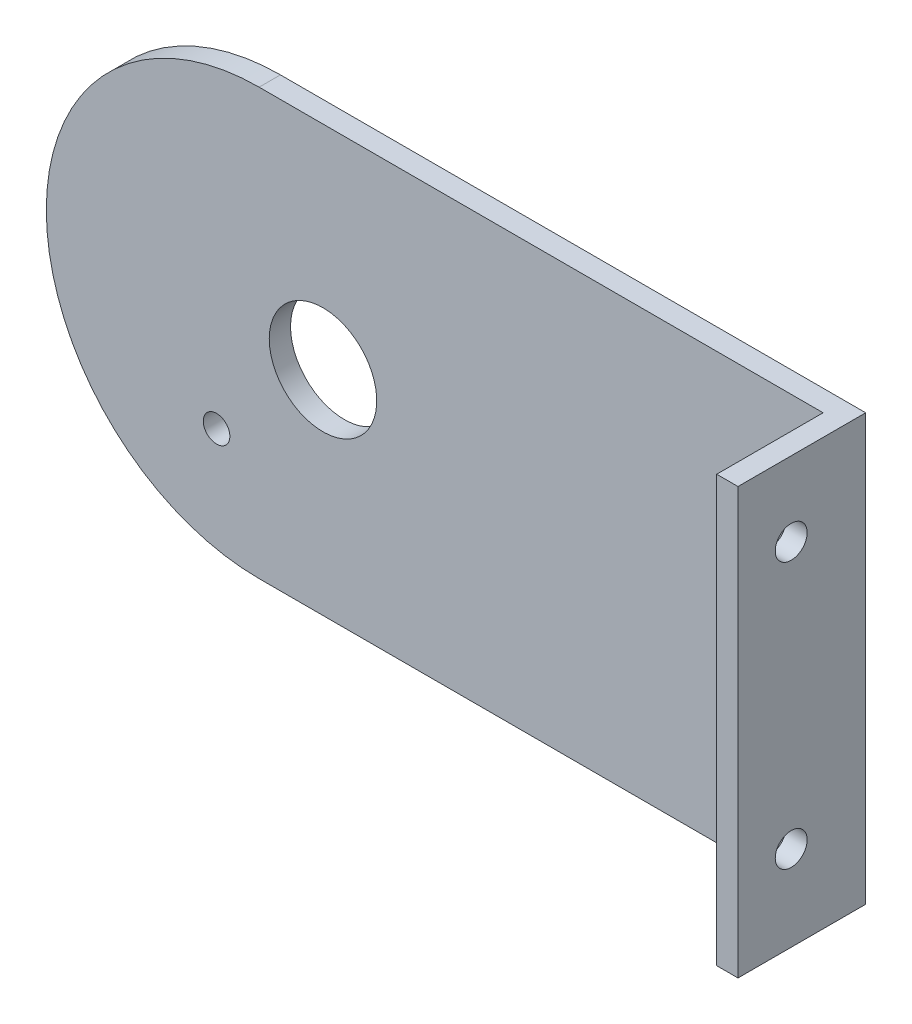
SolidWorks part; units mm, degrees
ref_plane "前视基准面" through (0, 0, 0) normal (0, 0, 1) x (1, 0, 0)
ref_plane "上视基准面" through (0, 0, 0) normal (0, 1, 0) x (1, 0, 0)
ref_plane "右视基准面" through (0, 0, 0) normal (1, 0, 0) x (0, 0, -1)
other "Configuration Table"
sketch "草图2" plane through (0, 0, 0) normal (0, 0, 1) x (1, 0, 0)
  line L0 (0, 0) -> (0, 40)
  line L1 (0, 40) -> (75, 40)
  line L2 (75, 40) -> (75, 0)
  line L3 (75, 0) -> (0, 0)
  dimension "D1" = 40
  dimension "D2" = 75
extrude "凸台-拉伸1" add sketch "草图2" along normal blind 2
sketch "草图3" plane through (0, 0, 0) normal (0, 0, -1) x (-1, 0, 0)
  line L1 (0, 40) -> (0, 0) construction
  line L2 (-75, 0) -> (-75, 40) construction
  line L6 (-75, 40) -> (0, 40) construction
  circle A0 centre (-26, 20) radius 5.05
  circle A8 centre (-16, 10.202) radius 1.25
  dimension "D1" = 10.1
  dimension "D4" = 9.798
  dimension "D5" = 20
  dimension "D9" = 2.5
  dimension "D2" = 26
  dimension "D3" = 75
  dimension "D10" = 10
extrude "切除-拉伸1" cut sketch "草图3" against normal through all
fillet "圆角1" radius 20 2 edges at (0, 40, 1) (0, 0, 1)
sketch "草图7" plane through (0, 0, 0) normal (0, 0, -1) x (-1, 0, 0)
  line L0 (-75, 40) -> (-20, 40) construction
  line L1 (-75, 0) -> (-73, 0)
  line L2 (-75, 0) -> (-75, 40)
  line L3 (-75, 40) -> (-73, 40)
  line L4 (-73, 0) -> (-73, 40)
  dimension "D1" = 2
extrude "凸台-拉伸3" add sketch "草图7" against normal blind 12
sketch "草图8" plane through (73, 0, 0) normal (-1, 0, 0) x (0, 0, 1)
  line L0 (12, 40) -> (2, 40) construction
  line L2 (2, 0) -> (2, 40) construction
  circle A0 centre (7, 33) radius 1.5
  circle A1 centre (7, 8) radius 1.5
  dimension "D2" = 25
  dimension "D3" = 3
  dimension "D1" = 7
  dimension "D4" = 5
extrude "切除-拉伸2" cut sketch "草图8" against normal blind 10
